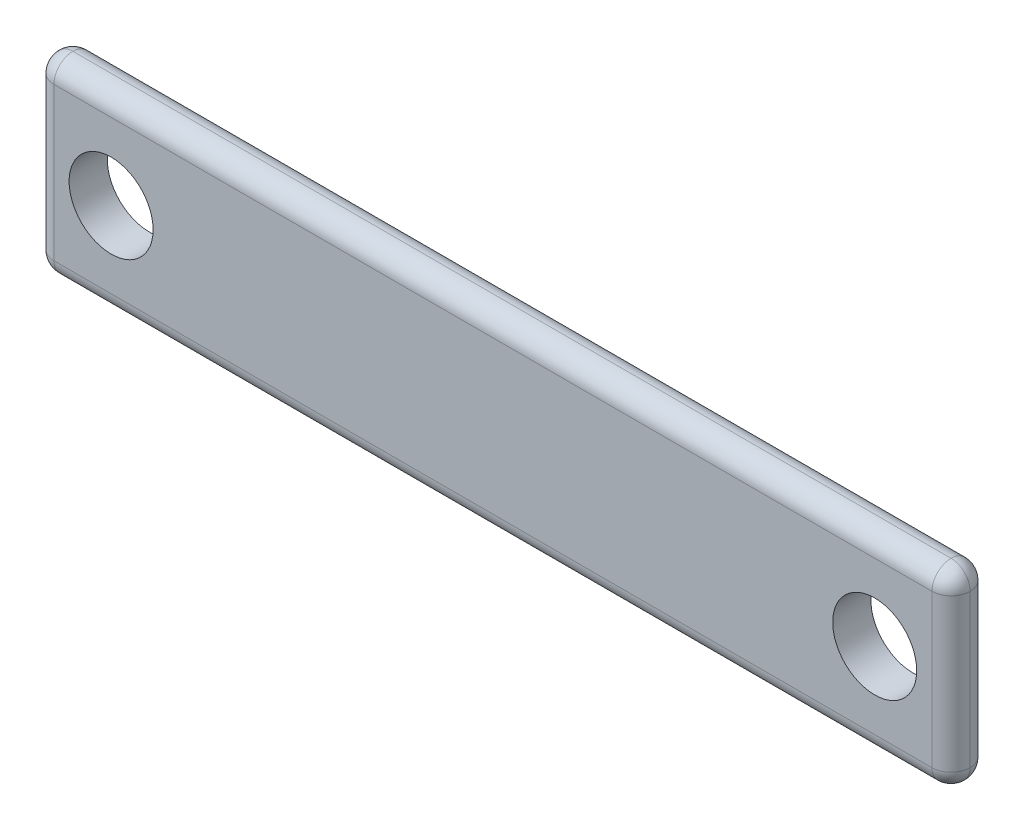
SolidWorks part; units mm, degrees
ref_plane "Plano frontal" through (0, 0, 0) normal (0, 0, 1) x (1, 0, 0)
ref_plane "Plano superior" through (0, 0, 0) normal (0, 1, 0) x (1, 0, 0)
ref_plane "Plano direito" through (0, 0, 0) normal (1, 0, 0) x (0, 0, -1)
sketch "Esboço1" plane through (0, 0, 0) normal (0, 0, 1) x (1, 0, 0)
  line L4 (0, 0) -> (0, 50)
  line L5 (0, 50) -> (240, 50)
  line L6 (240, 50) -> (240, 0)
  line L7 (240, 0) -> (0, 0)
  line L8 (0, 25) -> (240, 25) construction
  circle A0 centre (20, 25) radius 11
  circle A2 centre (220, 25) radius 11
  point P11 (120, 25)
  dimension "D3" = 22
  dimension "D4" = 22
  dimension "D5" = 100
  dimension "D1" = 240
  dimension "D2" = 50
  dimension "D6" = 100
extrude "Ressalto-extrusão1" add sketch "Esboço1" along normal blind 10
fillet "Filete1" radius 5 8 edges at (240, 25, 0) (240, 25, 10) (0, 25, 0) (0, 25, 10) (120, 0, 0) (120, 0, 10) (120, 50, 0) (120, 50, 10)
